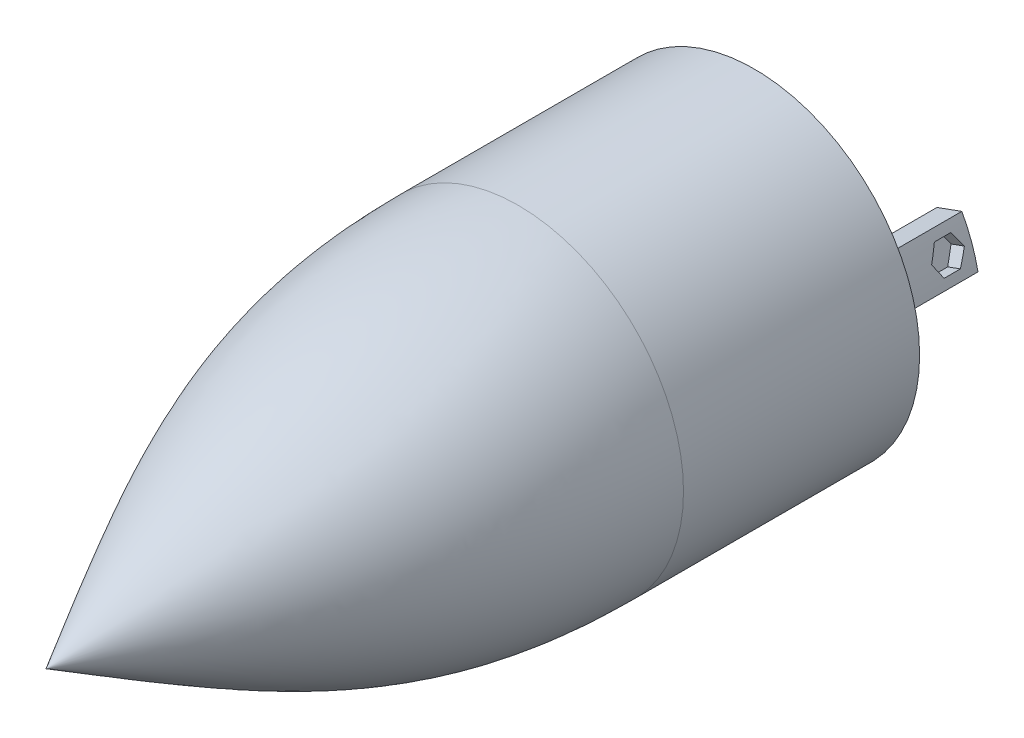
SolidWorks part; units mm, degrees
ref_plane "Front Plane" through (0, 0, 0) normal (0, 0, 1) x (1, 0, 0)
ref_plane "Top Plane" through (0, 0, 0) normal (0, 1, 0) x (1, 0, 0)
ref_plane "Right Plane" through (0, 0, 0) normal (1, 0, 0) x (0, 0, -1)
sketch "Sketch4" plane through (0, 0, 0) normal (0, 0, 1) x (1, 0, 0)
  circle A1 centre (0, 0) radius 35
  dimension "D1" = 70
extrude "Boss-Extrude10" add sketch "Sketch4" along normal blind 150
sketch "Sketch24" plane through (0, 0, 0) normal (1, 0, 0) x (0, 0, -1)
  line L0 (-50, 35) -> (-50, -35)
  line L1 (0, 35) -> (-150, 35) construction
  line L2 (-150, -35) -> (0, -35) construction
  line L3 (-150, 35) -> (-150, -35) construction
  line L4 (-150, 0) -> (-163.533, 0)
  line L5 (-163.533, 0) -> (-163.533, 49.8581)
  line L6 (-163.533, 49.8581) -> (-50, 49.8581)
  line L7 (-50, 49.8581) -> (-50, 35)
  line L8 (-150, 0) -> (3.4372, 0) construction
  spline S0 degree 3 poles (-50, 35) (-89.421, 35) (-111.5732, 21.9684) (-150, 0) knots 0 0 0 0 1 1 1 1
  point P14 (-150, 0)
revolve "Cut-Revolve5" cut sketch "Sketch24" angle 360 about L8 region at (0, 32.3453, 120.3733)
shell "Shell11" thickness 2 removed face at (35, 0, 0)
sketch "Sketch25" plane through (0, 0, 0) normal (0, 0, 1) x (1, 0, 0)
  line L0 (0, 0) -> (0, -39.6781) construction
  line L1 (0, 0) -> (-52.7231, 19.1896) construction
  line L2 (0, 0) -> (56.9626, 20.7327) construction
  line L3 (32.3619, 6.4579) -> (27.0818, 4.5361)
  line L4 (27.0818, 4.5361) -> (23.6616, 13.933)
  line L5 (23.6616, 13.933) -> (28.9417, 15.8548)
  line L6 (-28.9417, 15.8548) -> (-23.6616, 13.933)
  line L7 (-23.6616, 13.933) -> (-27.0818, 4.5361)
  line L8 (-27.0818, 4.5361) -> (-32.3619, 6.4579)
  line L9 (-5, -32.619) -> (-5, -27)
  line L10 (-5, -27) -> (5, -27)
  line L11 (5, -27) -> (5, -32.619)
  circle A0 centre (0, 0) radius 33 construction
  arc A1 (32.3619, 6.4579) -> (28.9417, 15.8548) centre (0, 0) ccw
  arc A2 (-28.9417, 15.8548) -> (-32.3619, 6.4579) centre (0, 0) ccw
  arc A3 (-5, -32.619) -> (5, -32.619) centre (0, 0) ccw
  circle A4 centre (0, 0) radius 33 construction
  point P7 (-31.7758, 8.905)
  point P10 (29.0436, 11.7179)
  point P13 (30.3296, 13.0044)
  point P14 (0, 0)
  point P15 (0, 0)
  point P16 (0, 0)
  point P17 (0, 0)
  point P18 (25.3717, 9.2345)
  point P23 (-25.3717, 9.2345)
  point P29 (0, -27)
  point P30 (-1.4505, -32.9681)
  point P31 (3.568, -32.8065)
  point P34 (-28.7847, -16.1382)
  point P35 (-30.3605, 12.9321)
  dimension "D1" = 110
  dimension "D2" = 110
  dimension "D3" = 10
  dimension "D4" = 27
  dimension "D5" = 27
  dimension "D6" = 27
  dimension "D7" = 10
  dimension "D8" = 10
extrude "Boss-Extrude11" add sketch "Sketch25" along normal up to next
extrude "Boss-Extrude12" add sketch "Sketch25<2>" against normal blind 15
sketch "Sketch25<2>" plane through (0, 0, 0) normal (0, 0, 1) x (1, 0, 0) same geometry as "Sketch25"
ref_plane "Plane3" through (31.0099, 11.2867, 0) normal (-0.9397, -0.342, 0) x (0, 0, 1)
ref_plane "Plane4" through (-31.0099, 11.2867, 0) normal (0.9397, -0.342, 0) x (0, 0, -1)
ref_plane "Plane5" through (0, -33, 0) normal (0, 1, 0) x (1, 0, 0)
sketch "Sketch26" plane through (31.0099, 11.2867, 0) normal (-0.9397, -0.342, 0) x (0, 0, 1)
  line L1 (-8.2688, -3.0005) -> (-6.5359, -0.0009)
  line L2 (-6.5359, -0.0009) -> (-8.2671, 2.9995)
  line L3 (-8.2671, 2.9995) -> (-11.7312, 3.0005)
  line L4 (-11.7312, 3.0005) -> (-13.4641, 0.0009)
  line L5 (-13.4641, 0.0009) -> (-11.7329, -2.9995)
  line L6 (-11.7329, -2.9995) -> (-8.2688, -3.0005)
  circle A0 centre (-10, 0) radius 3 construction
  dimension "D1" = 10
  dimension "D2" = 6
extrude "Cut-Extrude7" cut sketch "Sketch26" along normal blind 3
sketch "Sketch27" plane through (-31.0099, 11.2867, 0) normal (0.9397, -0.342, 0) x (0, 0, -1)
  line L1 (11.6993, -3.0187) -> (13.4639, -0.0377)
  line L2 (13.4639, -0.0377) -> (11.7646, 2.981)
  line L3 (11.7646, 2.981) -> (8.3007, 3.0187)
  line L4 (8.3007, 3.0187) -> (6.5361, 0.0377)
  line L5 (6.5361, 0.0377) -> (8.2354, -2.981)
  line L6 (8.2354, -2.981) -> (11.6993, -3.0187)
  circle A0 centre (10, 0) radius 3 construction
  dimension "D1" = 10
  dimension "D2" = 6
extrude "Cut-Extrude8" cut sketch "Sketch27" along normal blind 3
sketch "Sketch28" plane through (0, -33, 0) normal (0, 1, 0) x (1, 0, 0)
  line L1 (0, 13.4641) -> (-3, 11.7321)
  line L2 (-3, 11.7321) -> (-3, 8.2679)
  line L3 (-3, 8.2679) -> (0, 6.5359)
  line L4 (0, 6.5359) -> (3, 8.2679)
  line L5 (3, 8.2679) -> (3, 11.7321)
  line L6 (3, 11.7321) -> (0, 13.4641)
  circle A0 centre (0, 10) radius 3 construction
  dimension "D1" = 10
  dimension "D2" = 6
extrude "Cut-Extrude9" cut sketch "Sketch28" along normal blind 3
sketch "Sketch29" plane through (0, 0, 0) normal (0, 0, 1) x (1, 0, 0)
  line L0 (28.8617, 16) -> (-28.8617, 16)
  arc A0 (28.9417, 15.8548) -> (-28.9417, 15.8548) centre (0, 0) ccw construction
  arc A1 (28.8617, 16) -> (-28.8617, 16) centre (0, 0) ccw
  dimension "D1" = 16
extrude "Boss-Extrude13" add sketch "Sketch29" along normal blind 15
sketch "Sketch30" plane through (0, 0, 0) normal (0, 0, -1) x (-1, 0, 0)
  line L0 (-24.367, 17.5) -> (24.367, 17.5)
  arc A1 (24.367, 17.5) -> (-24.367, 17.5) centre (0, 0) ccw
  dimension "D2" = 60
  dimension "D1" = 17.5
extrude "Cut-Extrude10" cut sketch "Sketch30" against normal up to next
fillet "Fillet4" radius 8 1 edges at (0, 33, 15)
equation "\"fuse_diam\"= 0.07"
equation "\"fuse_rad\"= 0.035"
equation "\"battery_length\"= 0.076"
equation "\"battery_width\"= 0.034"
equation "\"battery_height\"= 0.051"
equation "\"bat_bay_length\"= 0.096"
equation "\"shell\"= 0.002"
equation "\"wing_shelf\"= 0.0175"
equation "\"chord_length\"= 0.089"
equation "\"tail_length\"= 0.26532000000000006"
equation "\"tail_diam\"= 0.035"
equation "\"connector\"= 0.06633000000000001"
equation "\"D1@Sketch4\"=\"fuse_diam\""
equation "\"D1@Sketch24\"=.05"
equation "\"D4@Sketch25\"=\"fuse_rad\"-.008"
equation "\"D5@Sketch25\"=\"fuse_rad\"-0.008"
equation "\"D6@Sketch25\"=\"fuse_rad\"-0.008"
equation "\"D1@Sketch29\"=\"wing_shelf\" -0.0015"
equation "\"D2@Sketch30\"=\"fuse_diam\"-0.01"
equation "\"D1@Sketch30\"=\"wing_shelf\""
